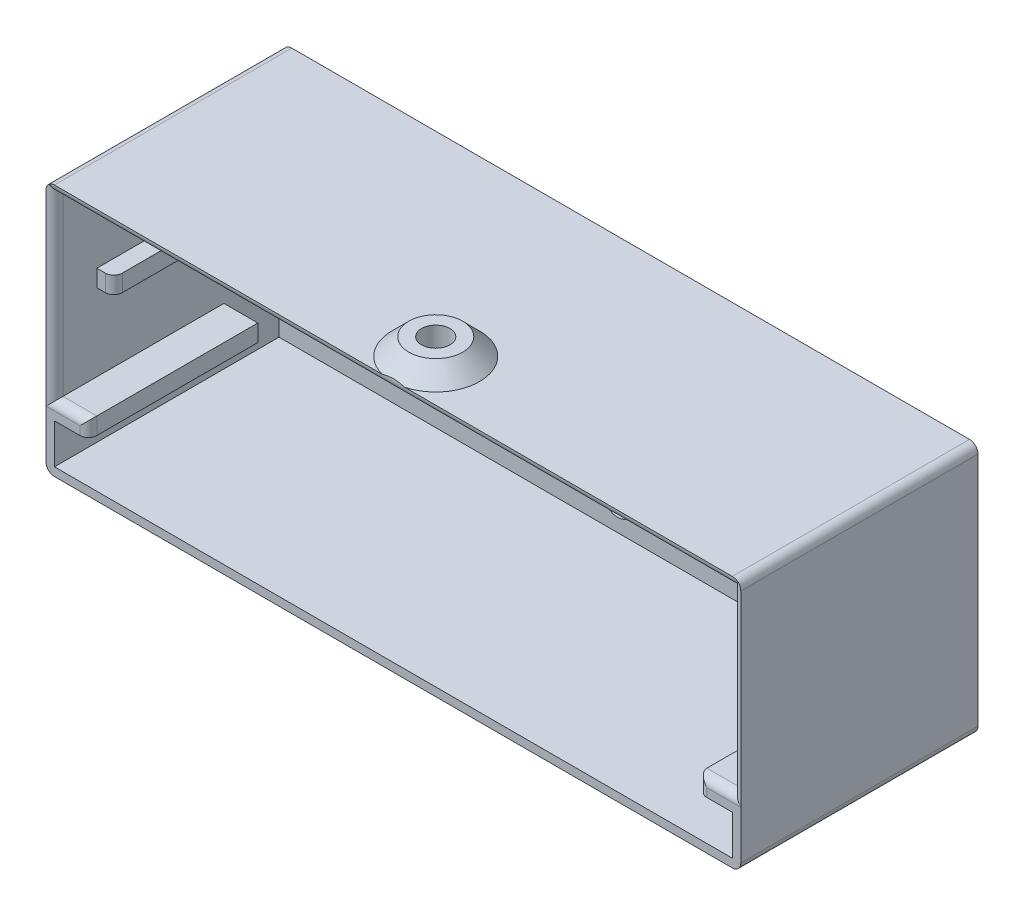
SolidWorks part; units mm, degrees
ref_plane "Front Plane" through (0, 0, 0) normal (0, 0, 1) x (1, 0, 0)
ref_plane "Top Plane" through (0, 0, 0) normal (0, 1, 0) x (1, 0, 0)
ref_plane "Right Plane" through (0, 0, 0) normal (1, 0, 0) x (0, 0, -1)
sketch "Sketch1" plane through (0, 0, 0) normal (0, 0, 1) x (1, 0, 0)
  line L1 (41, -14.9) -> (-41, -14.9)
  line L2 (41, -14.9) -> (41, 14.9)
  line L3 (41, 14.9) -> (-41, 14.9)
  line L4 (-41, -14.9) -> (-41, 14.9)
  line L5 (41, -14.9) -> (-41, 14.9) construction
  line L6 (41, 14.9) -> (-41, -14.9) construction
  point P0 (0, 0)
  dimension "D1" = 29.8
  dimension "D2" = 82
extrude "Boss-Extrude1" add sketch "Sketch1" along normal blind 3
sketch "Sketch2" plane through (0, 0, 3) normal (0, 0, 1) x (1, 0, 0)
  line L1 (41, -14.9) -> (-41, -14.9)
  line L2 (41, -14.9) -> (41, 14.9)
  line L3 (41, 14.9) -> (-41, 14.9)
  line L4 (-41, -14.9) -> (-41, 14.9)
  line L5 (41, -14.9) -> (-41, 14.9) construction
  line L6 (41, 14.9) -> (-41, -14.9) construction
  line L7 (40, -13.9) -> (-40, -13.9)
  line L8 (40, -13.9) -> (40, 13.9)
  line L9 (40, 13.9) -> (-40, 13.9)
  line L10 (-40, -13.9) -> (-40, 13.9)
  line L11 (40, -13.9) -> (-40, 13.9) construction
  line L12 (40, 13.9) -> (-40, -13.9) construction
  point P0 (0, 0)
  point P7 (0, 0)
  dimension "D1" = 1
  dimension "D2" = 1
extrude "Boss-Extrude2" add sketch "Sketch2" along normal blind 25
sketch "Sketch3" plane through (0, 0, 3) normal (0, 0, 1) x (1, 0, 0)
  line L0 (-40, 13.9) -> (-40, -13.9) construction
  line L1 (-40, -7.2) -> (-36, -7.2)
  line L2 (-40, -7.2) -> (-40, -9.2)
  line L3 (-40, -9.2) -> (-36, -9.2)
  line L4 (-36, -7.2) -> (-36, -9.2)
  line L5 (40, -13.9) -> (40, 13.9) construction
  line L6 (40, -7.2) -> (36, -7.2)
  line L7 (40, -7.2) -> (40, -9.2)
  line L8 (40, -9.2) -> (36, -9.2)
  line L9 (36, -7.2) -> (36, -9.2)
  line L10 (40, 13.9) -> (-40, 13.9) construction
  line L11 (40, 13.9) -> (-40, 13.9) construction
  dimension "D1" = 2
  dimension "D2" = 2
  dimension "D3" = 4
  dimension "D4" = 4
  dimension "D5" = 21.1
  dimension "D6" = 21.1
extrude "Boss-Extrude3" add sketch "Sketch3" along normal up to surface (25 mm away) from offset 5 up to face at (0, 0, 28)
sketch "Sketch11" plane through (0, 14.9, 0) normal (0, 1, 0) x (1, 0, 0)
  line L0 (41, -28) -> (-41, -28) construction
  line L1 (-41, -28) -> (-41, 0) construction
  circle A0 centre (0, -23) radius 1.675
  dimension "D1" = 5
  dimension "D2" = 41
  dimension "D3" = 3.35
extrude "Cut-Extrude5" cut sketch "Sketch11" against normal up to surface (1 mm away) contours A0 up to face at (0, 13.9, 15.5)
sketch "Sketch13" plane through (0, 0, 0) normal (0, 0, -1) x (-1, 0, 0)
  line L0 (41, -14.9) -> (-41, -14.9) construction
  line L1 (-39, -6.9) -> (-30, -6.9)
  line L2 (-39, -6.9) -> (-39, -12.9)
  line L3 (-39, -12.9) -> (-30, -12.9)
  line L4 (-30, -6.9) -> (-30, -12.9)
  line L5 (-41, -14.9) -> (-41, 14.9) construction
  line L6 (-41, 14.9) -> (41, 14.9) construction
  line L7 (41, 14.9) -> (41, -14.9) construction
  circle A0 centre (0, 3.35) radius 1.675
  circle A1 centre (0, -10.65) radius 1.675
  dimension "D5" = 11.55
  dimension "D6" = 3.35
  dimension "D7" = 14
  dimension "D8" = 41
  dimension "D9" = 41
  dimension "D1" = 6
  dimension "D2" = 9
  dimension "D3" = 2
  dimension "D4" = 2
extrude "Cut-Extrude6" cut sketch "Sketch13" against normal up to surface (3 mm away) up to face at (0, 0, 3)
chamfer "Chamfer1" distance 5 angle 45 1 edges at (36, -8.2, 8)
sketch "Sketch14" plane through (0, 0, 3) normal (0, 0, 1) x (1, 0, 0)
  line L0 (-40, 13.9) -> (-40, -7.2) construction
  line L1 (-40, 3.9) -> (-38, 3.9)
  line L2 (-40, 3.9) -> (-40, 1.9)
  line L3 (-40, 1.9) -> (-38, 1.9)
  line L4 (-38, 3.9) -> (-38, 1.9)
  line L5 (40, -7.2) -> (40, 13.9) construction
  line L6 (40, 3.9) -> (38, 3.9)
  line L7 (40, 3.9) -> (40, 1.9)
  line L8 (40, 1.9) -> (38, 1.9)
  line L9 (38, 3.9) -> (38, 1.9)
  line L10 (40, 13.9) -> (-40, 13.9) construction
  line L11 (40, 13.9) -> (-40, 13.9) construction
  dimension "D1" = 2
  dimension "D2" = 2
  dimension "D3" = 2
  dimension "D4" = 2
  dimension "D5" = 10
  dimension "D6" = 10
extrude "Boss-Extrude4" add sketch "Sketch14" along normal blind 10 from offset 10
fillet "Fillet1" radius 1 9 edges at (-36, -8.2, 28) (-38, -7.2, 28) (-40, 3.35, 28) (0, 13.9, 28) (38, 2.9, 23) (38, -7.2, 28) (40, 3.35, 28) (36, -8.2, 28) (-38, 2.9, 23)
sketch "Sketch15" plane through (0, 14.9, 0) normal (0, 1, 0) x (1, 0, 0)
  circle A0 centre (0, -23) radius 1.675
  circle A1 centre (0, -23) radius 3.175
  circle A2 centre (0, -23) radius 1.675 construction
  dimension "D1" = 1.5
extrude "Boss-Extrude5" add sketch "Sketch15" along normal blind 2
chamfer "Chamfer2" distance 2 angle 45 1 edges at (3.175, 14.9, 23)
chamfer "Chamfer3" distance 2 angle 45 2 edges at (-40, 2.9, 13) (40, 2.9, 13)
sketch "Sketch16" plane through (0, 0, 3) normal (0, 0, 1) x (1, 0, 0)
  line L0 (-40, 13.9) -> (-40, -13.9) construction
  line L1 (-40, 13.9) -> (40, 13.9)
  line L2 (-40, 13.9) -> (-40, -13.9)
  line L3 (-40, -13.9) -> (40, -13.9)
  line L4 (40, 13.9) -> (40, -13.9)
  line L5 (40, 13.9) -> (-40, 13.9) construction
  line L6 (-40, -13.9) -> (40, -13.9) construction
  line L7 (40, -13.9) -> (40, 13.9) construction
extrude "Cut-Extrude7" cut sketch "Sketch16" against normal blind 1.5
fillet "Fillet2" radius 1 4 edges at (41, -14.9, 14) (41, 14.9, 14) (-41, 14.9, 14) (-41, -14.9, 14)
